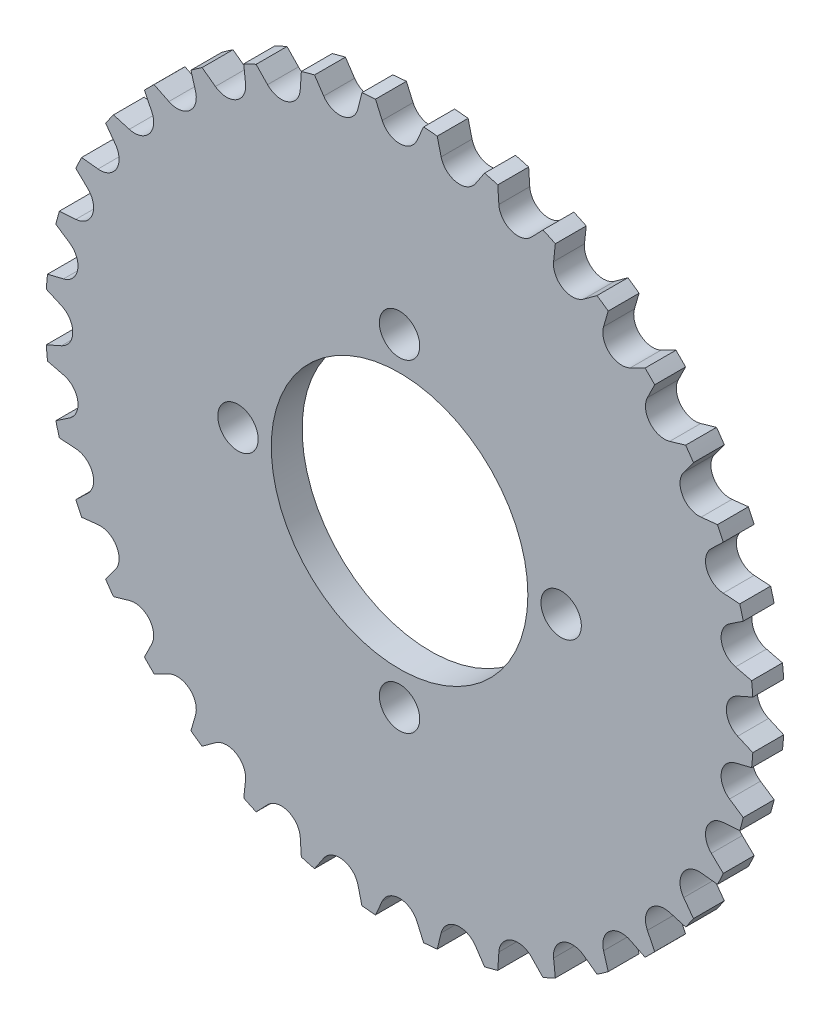
SolidWorks part; units mm, degrees
material "Plain Carbon Steel"
ref_plane "Front Plane" through (0, 0, 0) normal (0, 0, 1) x (1, 0, 0)
ref_plane "Top Plane" through (0, 0, 0) normal (0, 1, 0) x (1, 0, 0)
ref_plane "Right Plane" through (0, 0, 0) normal (1, 0, 0) x (0, 0, -1)
sketch "Sketch1" plane through (0, 0, 0) normal (0, 0, 1) x (1, 0, 0)
  line L0 (3.6596, 71.1503) -> (5.6741, 75.716)
  line L1 (3.6596, 71.1503) -> (8.7511, 70.7049) construction
  line L2 (7.5601, 75.551) -> (8.7511, 70.7049)
  line L3 (3.6596, 71.1503) -> (0, 0) construction
  line L4 (0, 0) -> (8.7511, 70.7049) construction
  line L5 (15.9591, 69.4339) -> (18.7358, 73.5804)
  line L6 (20.5645, 73.0904) -> (20.8959, 68.1111)
  line L7 (27.7738, 65.6078) -> (31.2283, 69.2091)
  line L8 (32.9441, 68.409) -> (32.4058, 63.4478)
  line L9 (38.7445, 59.7882) -> (42.7719, 62.7349)
  line L10 (44.3227, 61.649) -> (42.9311, 56.8567)
  line L11 (48.538, 52.1519) -> (53.0159, 54.3546)
  line L12 (54.3546, 53.0159) -> (52.1519, 48.538)
  line L13 (56.8567, 42.9311) -> (61.649, 44.3227)
  line L14 (62.7349, 42.7719) -> (59.7882, 38.7445)
  line L15 (63.4478, 32.4058) -> (68.409, 32.9441)
  line L16 (69.2091, 31.2283) -> (65.6078, 27.7738)
  line L17 (68.1111, 20.8959) -> (73.0904, 20.5645)
  line L18 (73.5804, 18.7358) -> (69.4339, 15.9591)
  line L19 (70.7049, 8.7511) -> (75.551, 7.5601)
  line L20 (75.716, 5.6741) -> (71.1503, 3.6596)
  line L21 (71.1503, -3.6596) -> (75.716, -5.6741)
  line L22 (75.551, -7.5601) -> (70.7049, -8.7511)
  line L23 (69.4339, -15.9591) -> (73.5804, -18.7358)
  line L24 (73.0904, -20.5645) -> (68.1111, -20.8959)
  line L25 (65.6078, -27.7738) -> (69.2091, -31.2283)
  line L26 (68.409, -32.9441) -> (63.4478, -32.4058)
  line L27 (59.7882, -38.7445) -> (62.7349, -42.7719)
  line L28 (61.649, -44.3227) -> (56.8567, -42.9311)
  line L29 (52.1519, -48.538) -> (54.3546, -53.0159)
  line L30 (53.0159, -54.3546) -> (48.538, -52.1519)
  line L31 (42.9311, -56.8567) -> (44.3227, -61.649)
  line L32 (42.7719, -62.7349) -> (38.7445, -59.7882)
  line L33 (32.4058, -63.4478) -> (32.9441, -68.409)
  line L34 (31.2283, -69.2091) -> (27.7738, -65.6078)
  line L35 (20.8959, -68.1111) -> (20.5645, -73.0904)
  line L36 (18.7358, -73.5804) -> (15.9591, -69.4339)
  line L37 (8.7511, -70.7049) -> (7.5601, -75.551)
  line L38 (5.6741, -75.716) -> (3.6596, -71.1503)
  line L39 (-3.6596, -71.1503) -> (-5.6741, -75.716)
  line L40 (-7.5601, -75.551) -> (-8.7511, -70.7049)
  line L41 (-15.9591, -69.4339) -> (-18.7358, -73.5804)
  line L42 (-20.5645, -73.0904) -> (-20.8959, -68.1111)
  line L43 (-27.7738, -65.6078) -> (-31.2283, -69.2091)
  line L44 (-32.9441, -68.409) -> (-32.4058, -63.4478)
  line L45 (-38.7445, -59.7882) -> (-42.7719, -62.7349)
  line L46 (-44.3227, -61.649) -> (-42.9311, -56.8567)
  line L47 (-48.538, -52.1519) -> (-53.0159, -54.3546)
  line L48 (-54.3546, -53.0159) -> (-52.1519, -48.538)
  line L49 (-56.8567, -42.9311) -> (-61.649, -44.3227)
  line L50 (-62.7349, -42.7719) -> (-59.7882, -38.7445)
  line L51 (-63.4478, -32.4058) -> (-68.409, -32.9441)
  line L52 (-69.2091, -31.2283) -> (-65.6078, -27.7738)
  line L53 (-68.1111, -20.8959) -> (-73.0904, -20.5645)
  line L54 (-73.5804, -18.7358) -> (-69.4339, -15.9591)
  line L55 (-70.7049, -8.7511) -> (-75.551, -7.5601)
  line L56 (-75.716, -5.6741) -> (-71.1503, -3.6596)
  line L57 (-71.1503, 3.6596) -> (-75.716, 5.6741)
  line L58 (-75.551, 7.5601) -> (-70.7049, 8.7511)
  line L59 (-69.4339, 15.9591) -> (-73.5804, 18.7358)
  line L60 (-73.0904, 20.5645) -> (-68.1111, 20.8959)
  line L61 (-65.6078, 27.7738) -> (-69.2091, 31.2283)
  line L62 (-68.409, 32.9441) -> (-63.4478, 32.4058)
  line L63 (-59.7882, 38.7445) -> (-62.7349, 42.7719)
  line L64 (-61.649, 44.3227) -> (-56.8567, 42.9311)
  line L65 (-52.1519, 48.538) -> (-54.3546, 53.0159)
  line L66 (-53.0159, 54.3546) -> (-48.538, 52.1519)
  line L67 (-42.9311, 56.8567) -> (-44.3227, 61.649)
  line L68 (-42.7719, 62.7349) -> (-38.7445, 59.7882)
  line L69 (-32.4058, 63.4478) -> (-32.9441, 68.409)
  line L70 (-31.2283, 69.2091) -> (-27.7738, 65.6078)
  line L71 (-20.8959, 68.1111) -> (-20.5645, 73.0904)
  line L72 (-18.7358, 73.5804) -> (-15.9591, 69.4339)
  line L73 (-8.7511, 70.7049) -> (-7.5601, 75.551)
  line L74 (-5.6741, 75.716) -> (-3.6596, 71.1503)
  line L83 (0, 72.765) -> (0, 0) construction
  line L84 (0, 0) -> (6.589, 75.3123) construction
  circle A0 centre (0, 0) radius 72.765 construction
  arc A1 (-3.9985, 72.6551) -> (3.6596, 71.1503) centre (0, 72.765) ccw
  arc A2 (4.3155, 72.6369) -> (8.3633, 72.2828) centre (0, 0) cw
  arc A3 (5.6741, 75.716) -> (7.5601, 75.551) centre (6.589, 75.3123) cw
  arc A4 (8.6787, 72.2456) -> (15.9591, 69.4339) centre (12.6355, 71.6595) ccw
  arc A5 (18.7358, 73.5804) -> (20.5645, 73.0904) centre (19.5667, 73.024) cw
  arc A6 (21.0921, 69.641) -> (27.7738, 65.6078) centre (24.8871, 68.3767) ccw
  arc A7 (31.2283, 69.2091) -> (32.9441, 68.409) centre (31.9499, 68.5169) cw
  arc A8 (32.8647, 64.9204) -> (38.7445, 59.7882) centre (36.3825, 63.0163) ccw
  arc A9 (42.7719, 62.7349) -> (44.3227, 61.649) centre (43.3624, 61.9279) cw
  arc A10 (43.6388, 58.2272) -> (48.538, 52.1519) centre (46.7724, 55.7412) ccw
  arc A11 (53.0159, 54.3546) -> (54.3546, 53.0159) centre (53.4573, 53.4573) cw
  arc A12 (53.0868, 49.7648) -> (56.8567, 42.9311) centre (55.7412, 46.7724) ccw
  arc A13 (61.649, 44.3227) -> (62.7349, 42.7719) centre (61.9279, 43.3624) cw
  arc A14 (60.9219, 39.7903) -> (63.4478, 32.4058) centre (63.0163, 36.3825) ccw
  arc A15 (68.409, 32.9441) -> (69.2091, 31.2283) centre (68.5169, 31.9499) cw
  arc A16 (66.9059, 28.6068) -> (68.1111, 20.8959) centre (68.3767, 24.8871) ccw
  arc A17 (73.0904, 20.5645) -> (73.5804, 18.7358) centre (73.024, 19.5667) cw
  arc A18 (70.8569, 16.5542) -> (70.7049, 8.7511) centre (71.6595, 12.6355) ccw
  arc A19 (75.551, 7.5601) -> (75.716, 5.6741) centre (75.3123, 6.589) cw
  arc A20 (72.6551, 3.9985) -> (71.1503, -3.6596) centre (72.765, 0) ccw
  arc A21 (75.716, -5.6741) -> (75.551, -7.5601) centre (75.3123, -6.589) cw
  arc A22 (72.2456, -8.6787) -> (69.4339, -15.9591) centre (71.6595, -12.6355) ccw
  arc A23 (73.5804, -18.7358) -> (73.0904, -20.5645) centre (73.024, -19.5667) cw
  arc A24 (69.641, -21.0921) -> (65.6078, -27.7738) centre (68.3767, -24.8871) ccw
  arc A25 (69.2091, -31.2283) -> (68.409, -32.9441) centre (68.5169, -31.9499) cw
  arc A26 (64.9204, -32.8647) -> (59.7882, -38.7445) centre (63.0163, -36.3825) ccw
  arc A27 (62.7349, -42.7719) -> (61.649, -44.3227) centre (61.9279, -43.3624) cw
  arc A28 (58.2272, -43.6388) -> (52.1519, -48.538) centre (55.7412, -46.7724) ccw
  arc A29 (54.3546, -53.0159) -> (53.0159, -54.3546) centre (53.4573, -53.4573) cw
  arc A30 (49.7648, -53.0868) -> (42.9311, -56.8567) centre (46.7724, -55.7412) ccw
  arc A31 (44.3227, -61.649) -> (42.7719, -62.7349) centre (43.3624, -61.9279) cw
  arc A32 (39.7903, -60.9219) -> (32.4058, -63.4478) centre (36.3825, -63.0163) ccw
  arc A33 (32.9441, -68.409) -> (31.2283, -69.2091) centre (31.9499, -68.5169) cw
  arc A34 (28.6068, -66.9059) -> (20.8959, -68.1111) centre (24.8871, -68.3767) ccw
  arc A35 (20.5645, -73.0904) -> (18.7358, -73.5804) centre (19.5667, -73.024) cw
  arc A36 (16.5542, -70.8569) -> (8.7511, -70.7049) centre (12.6355, -71.6595) ccw
  arc A37 (7.5601, -75.551) -> (5.6741, -75.716) centre (6.589, -75.3123) cw
  arc A38 (3.9985, -72.6551) -> (-3.6596, -71.1503) centre (0, -72.765) ccw
  arc A39 (-5.6741, -75.716) -> (-7.5601, -75.551) centre (-6.589, -75.3123) cw
  arc A40 (-8.6787, -72.2456) -> (-15.9591, -69.4339) centre (-12.6355, -71.6595) ccw
  arc A41 (-18.7358, -73.5804) -> (-20.5645, -73.0904) centre (-19.5667, -73.024) cw
  arc A42 (-21.0921, -69.641) -> (-27.7738, -65.6078) centre (-24.8871, -68.3767) ccw
  arc A43 (-31.2283, -69.2091) -> (-32.9441, -68.409) centre (-31.9499, -68.5169) cw
  arc A44 (-32.8647, -64.9204) -> (-38.7445, -59.7882) centre (-36.3825, -63.0163) ccw
  arc A45 (-42.7719, -62.7349) -> (-44.3227, -61.649) centre (-43.3624, -61.9279) cw
  arc A46 (-43.6388, -58.2272) -> (-48.538, -52.1519) centre (-46.7724, -55.7412) ccw
  arc A47 (-53.0159, -54.3546) -> (-54.3546, -53.0159) centre (-53.4573, -53.4573) cw
  arc A48 (-53.0868, -49.7648) -> (-56.8567, -42.9311) centre (-55.7412, -46.7724) ccw
  arc A49 (-61.649, -44.3227) -> (-62.7349, -42.7719) centre (-61.9279, -43.3624) cw
  arc A50 (-60.9219, -39.7903) -> (-63.4478, -32.4058) centre (-63.0163, -36.3825) ccw
  arc A51 (-68.409, -32.9441) -> (-69.2091, -31.2283) centre (-68.5169, -31.9499) cw
  arc A52 (-66.9059, -28.6068) -> (-68.1111, -20.8959) centre (-68.3767, -24.8871) ccw
  arc A53 (-73.0904, -20.5645) -> (-73.5804, -18.7358) centre (-73.024, -19.5667) cw
  arc A54 (-70.8569, -16.5542) -> (-70.7049, -8.7511) centre (-71.6595, -12.6355) ccw
  arc A55 (-75.551, -7.5601) -> (-75.716, -5.6741) centre (-75.3123, -6.589) cw
  arc A56 (-72.6551, -3.9985) -> (-71.1503, 3.6596) centre (-72.765, 0) ccw
  arc A57 (-75.716, 5.6741) -> (-75.551, 7.5601) centre (-75.3123, 6.589) cw
  arc A58 (-72.2456, 8.6787) -> (-69.4339, 15.9591) centre (-71.6595, 12.6355) ccw
  arc A59 (-73.5804, 18.7358) -> (-73.0904, 20.5645) centre (-73.024, 19.5667) cw
  arc A60 (-69.641, 21.0921) -> (-65.6078, 27.7738) centre (-68.3767, 24.8871) ccw
  arc A61 (-69.2091, 31.2283) -> (-68.409, 32.9441) centre (-68.5169, 31.9499) cw
  arc A62 (-64.9204, 32.8647) -> (-59.7882, 38.7445) centre (-63.0163, 36.3825) ccw
  arc A63 (-62.7349, 42.7719) -> (-61.649, 44.3227) centre (-61.9279, 43.3624) cw
  arc A64 (-58.2272, 43.6388) -> (-52.1519, 48.538) centre (-55.7412, 46.7724) ccw
  arc A65 (-54.3546, 53.0159) -> (-53.0159, 54.3546) centre (-53.4573, 53.4573) cw
  arc A66 (-49.7648, 53.0868) -> (-42.9311, 56.8567) centre (-46.7724, 55.7412) ccw
  arc A67 (-44.3227, 61.649) -> (-42.7719, 62.7349) centre (-43.3624, 61.9279) cw
  arc A68 (-39.7903, 60.9219) -> (-32.4058, 63.4478) centre (-36.3825, 63.0163) ccw
  arc A69 (-32.9441, 68.409) -> (-31.2283, 69.2091) centre (-31.9499, 68.5169) cw
  arc A70 (-28.6068, 66.9059) -> (-20.8959, 68.1111) centre (-24.8871, 68.3767) ccw
  arc A71 (-20.5645, 73.0904) -> (-18.7358, 73.5804) centre (-19.5667, 73.024) cw
  arc A72 (-16.5542, 70.8569) -> (-8.7511, 70.7049) centre (-12.6355, 71.6595) ccw
  arc A73 (-7.5601, 75.551) -> (-5.6741, 75.716) centre (-6.589, 75.3123) cw
  point P289 (0, 0)
  dimension "D1" = 145.53
  dimension "D2" = 4
  dimension "D5" = 1
  dimension "D6" = 75.6
  dimension "D3" = 5
  dimension "D4" = 36
extrude "Boss-Extrude1" add sketch "Sketch1" along normal blind 6.5 contours L74 A73 L73 A72 L72 A71 L71 A70 L70 A69 L69 A68 L68 A67 L67 A66 L66 A65 L65 A64 L64 A63 L63 A62 L62 A61 L61 A60 L60 A59 L59 A58 L58 A57 L57 A56 | A3 L0 A2 L2 region at (-0.0042, -0.0476, 0) region at (6.4786, 74.0508, 0)
sketch "Sketch5" plane through (0, 0, 0) normal (0, 0, -1) x (-1, 0, 0)
  line L0 (0, 68.765) -> (2.9886, 68.5035)
  line L1 (0, 68.765) -> (0.7057, 76.8309)
  line L2 (11.9409, 67.7203) -> (12.6466, 75.7862)
  line L3 (0.7057, 76.8309) -> (12.6466, 75.7862)
  line L4 (8.9523, 67.9818) -> (11.9409, 67.7203)
  arc A0 (2.9886, 68.5035) -> (8.9523, 67.9818) centre (6.4237, 73.4229) ccw
  arc A3 (-3.6596, 71.1503) -> (3.6596, 71.1503) centre (0, 72.765) ccw construction
  arc A5 (-3.6596, 71.1503) -> (3.6596, 71.1503) centre (0, 72.765) ccw construction
  arc A7 (8.7511, 70.7049) -> (15.9591, 69.4339) centre (12.6355, 71.6595) ccw construction
  arc A8 (7.5601, 75.551) -> (5.6741, 75.716) centre (6.589, 75.3123) ccw construction
  point P19 (0, 68.765)
  point P22 (11.9409, 67.7203)
  dimension "D2" = 3
  dimension "D3" = 3
  dimension "D4" = 6
extrude "Cut-Extrude2" [suppressed] cut sketch "Sketch5" against normal blind 10
sketch "Sketch9" plane through (0, 0, 0) normal (0, 0, -1) x (-1, 0, 0)
  circle A0 centre (0, 0) radius 74.5
  circle A1 centre (0, 0) radius 100
  dimension "D1" = 149
  dimension "D2" = 200
extrude "Cut-Extrude5" cut sketch "Sketch9" against normal blind 10
sketch "Sketch10" plane through (0, 0, 6.5) normal (0, 0, 1) x (1, 0, 0)
  circle A0 centre (0, 0) radius 27
  circle A1 centre (0, 34) radius 4.25
  circle A2 centre (34, 0) radius 4.25
  circle A3 centre (0, -34) radius 4.25
  circle A4 centre (-34, 0) radius 4.25
  point P5 (13.3816, -52.8817)
  point P6 (0, 0)
  point P14 (0, 0)
  dimension "D1" = 54
  dimension "D2" = 8.5
  dimension "D3" = 34
  dimension "D4" = 4
extrude "Cut-Extrude6" cut sketch "Sketch10" against normal through all
equation "\"Teeth\"= 36"
equation "\"D4@Sketch1\"=\"Teeth\""
equation "\"D6@Sketch1\"=84/40*\"Teeth\""
equation "\"D1@Sketch1\"=161.70/40*\"Teeth\""
equation "\"D3@Sketch1\"=4.5/\"Teeth\"*40"
